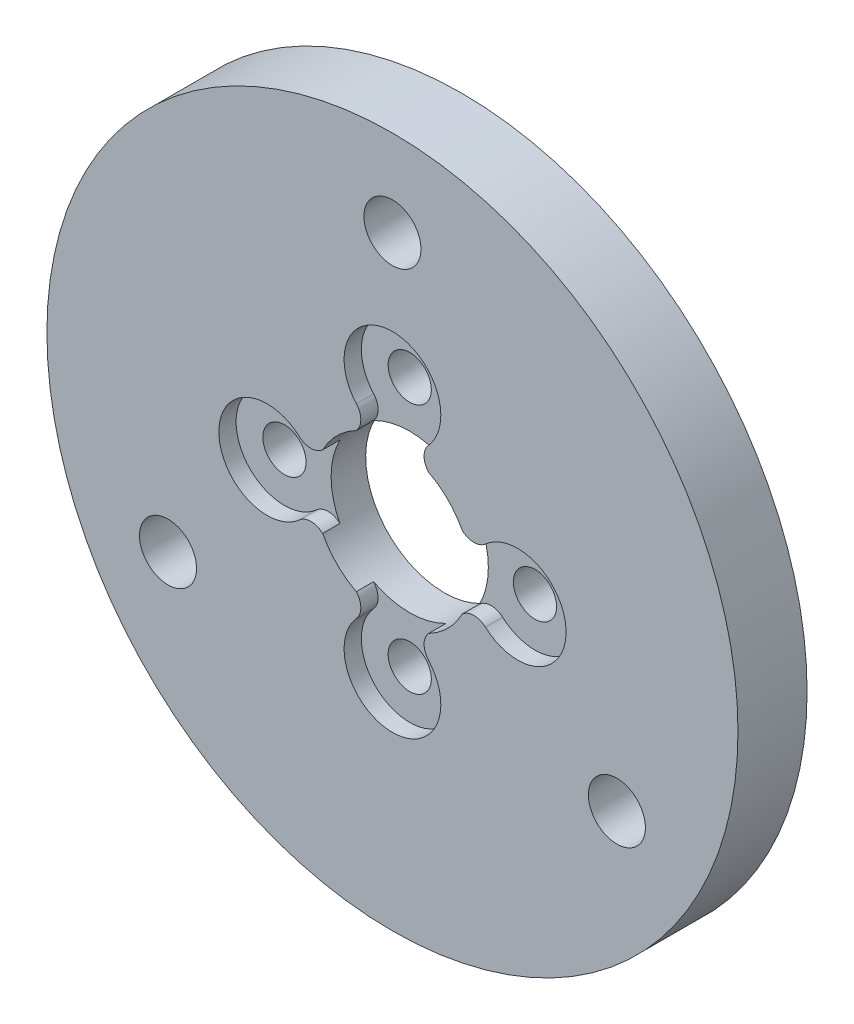
SolidWorks part; units mm, degrees
material "6061 合金"
ref_plane "前视基准面" through (0, 0, 0) normal (0, 0, 1) x (1, 0, 0)
ref_plane "上视基准面" through (0, 0, 0) normal (0, 1, 0) x (1, 0, 0)
ref_plane "右视基准面" through (0, 0, 0) normal (1, 0, 0) x (0, 0, -1)
other "Configuration Table"
sketch "草图1" plane through (0, 0, 0) normal (0, 0, 1) x (1, 0, 0)
  circle A0 centre (0, 0) radius 20
  circle A1 centre (0, 0) radius 4.55
  dimension "D1" = 40
  dimension "D2" = 9.1
extrude "凸台-拉伸1" add sketch "草图1" along normal blind 3
sketch "草图4" plane through (0, 0, 3) normal (0, 0, 1) x (1, 0, 0)
  circle A0 centre (0, 0) radius 7.25 construction
  circle A1 centre (0, 7.25) radius 1.25
  circle A2 centre (7.25, 0) radius 1.25
  circle A3 centre (0, -7.25) radius 1.25
  circle A4 centre (-7.25, 0) radius 1.25
  dimension "D1" = 14.5
  dimension "D2" = 2.5
extrude "切除-拉伸3" cut sketch "草图4" against normal blind 11
sketch "草图5" plane through (0, 0, 3) normal (0, 0, 1) x (1, 0, 0)
  circle A0 centre (0, -7.25) radius 1.25 construction
  circle A1 centre (-7.25, 0) radius 1.25 construction
  circle A2 centre (7.25, 0) radius 1.25 construction
  circle A3 centre (0, 7.25) radius 1.25 construction
  circle A4 centre (0, -7.25) radius 1.25
  circle A5 centre (-7.25, 0) radius 1.25
  circle A6 centre (7.25, 0) radius 1.25
  circle A7 centre (0, 7.25) radius 1.25
  arc A8 (-5.3824, 2.0861) -> (-5.3824, -2.0861) centre (-7.25, 0) ccw
  arc A9 (5.3824, -2.0861) -> (5.3824, 2.0861) centre (7.25, 0) ccw
  arc A10 (2.0861, 5.3824) -> (-2.0861, 5.3824) centre (0, 7.25) ccw
  arc A11 (-2.0861, -5.3824) -> (2.0861, -5.3824) centre (0, -7.25) ccw
  arc A12 (-3.858, -2.3164) -> (-2.3164, -3.858) centre (0, 0) ccw
  circle A13 centre (-7.25, 0) radius 2.8 construction
  circle A14 centre (0, 7.25) radius 2.8 construction
  arc A15 (-2.3164, 3.858) -> (-3.858, 2.3164) centre (0, 0) ccw
  circle A16 centre (7.25, 0) radius 2.8 construction
  arc A17 (3.858, 2.3164) -> (2.3164, 3.858) centre (0, 0) ccw
  circle A18 centre (0, -7.25) radius 2.8 construction
  arc A19 (2.3164, -3.858) -> (3.858, -2.3164) centre (0, 0) ccw
  arc A20 (-3.858, -2.3164) -> (-5.3824, -2.0861) centre (-4.7153, -2.8312) ccw
  arc A21 (-2.0861, -5.3824) -> (-2.3164, -3.858) centre (-2.8312, -4.7153) ccw
  arc A22 (2.0861, -5.3824) -> (2.3164, -3.858) centre (2.8312, -4.7153) cw
  arc A23 (3.858, -2.3164) -> (5.3824, -2.0861) centre (4.7153, -2.8312) cw
  arc A24 (3.858, 2.3164) -> (5.3824, 2.0861) centre (4.7153, 2.8312) ccw
  arc A25 (2.3164, 3.858) -> (2.0861, 5.3824) centre (2.8312, 4.7153) cw
  arc A26 (-2.3164, 3.858) -> (-2.0861, 5.3824) centre (-2.8312, 4.7153) ccw
  arc A27 (-3.858, 2.3164) -> (-5.3824, 2.0861) centre (-4.7153, 2.8312) cw
  point P36 (0.4146, -4.4809)
  point P41 (4.4809, 0.4146)
  point P46 (-0.4146, 4.4809)
  dimension "D2" = 1
  dimension "D1" = 5.6
extrude "切除-拉伸4" cut sketch "草图5" against normal blind 1
sketch "草图6" plane through (0, 0, 3) normal (0, 0, 1) x (1, 0, 0)
  circle A0 centre (0, 0) radius 17.5 construction
  circle A1 centre (0, 17.5) radius 1.65
  circle A2 centre (15.1554, -8.75) radius 1.65
  circle A3 centre (-15.1554, -8.75) radius 1.65
  point P11 (0, 0)
  dimension "D1" = 35
  dimension "D2" = 3.3
  dimension "D3" = 3
sketch "草图7" plane through (0, 0, 0) normal (0, 0, -1) x (-1, 0, 0)
  circle A0 centre (0, 7.25) radius 2.25 construction
  circle A1 centre (0, 0) radius 9.5
  circle A2 centre (0, 0) radius 20
  dimension "D1" = 4.5
  dimension "D2" = 40
extrude "凸台-拉伸2" add sketch "草图7" along normal mid plane 2
sketch "草图9" plane through (0, 0, -1) normal (0, 0, -1) x (-1, 0, 0)
  circle A0 centre (0, 0) radius 9.5
  circle A1 centre (0, 0) radius 20
extrude "凸台-拉伸3" add sketch "草图9" along normal blind 0.2
sketch "草图10" plane through (0, 0, -1.2) normal (0, 0, -1) x (-1, 0, 0)
  circle A0 centre (0, 0) radius 18.25 construction
  circle A1 centre (0, 0) radius 19.25
  circle A2 centre (0, 0) radius 17.25
  dimension "D1" = 36.5
  dimension "D2" = 1
  dimension "D3" = 1
extrude "切除-拉伸6" cut sketch "草图10" against normal blind 1
fillet "圆角1" radius 1 2 edges at (-17.25, 0, -0.2) (-19.25, 0, -0.2)
sketch "草图11" plane through (0, 0, -1.2) normal (0, 0, -1) x (-1, 0, 0)
  circle A0 centre (0, 0) radius 20
extrude "切除-拉伸7" cut sketch "草图11" against normal blind 0.2
sketch "草图13" plane through (0, 0, -1) normal (0, 0, -1) x (-1, 0, 0)
  circle A0 centre (0, 0) radius 15 construction
  circle A1 centre (0, 15) radius 1.65
  circle A2 centre (12.9904, -7.5) radius 1.65
  circle A3 centre (-12.9904, -7.5) radius 1.65
  point P11 (0, 0)
  dimension "D1" = 30
  dimension "D2" = 3.3
  dimension "D3" = 3
extrude "切除-拉伸8" cut sketch "草图13" against normal through all
